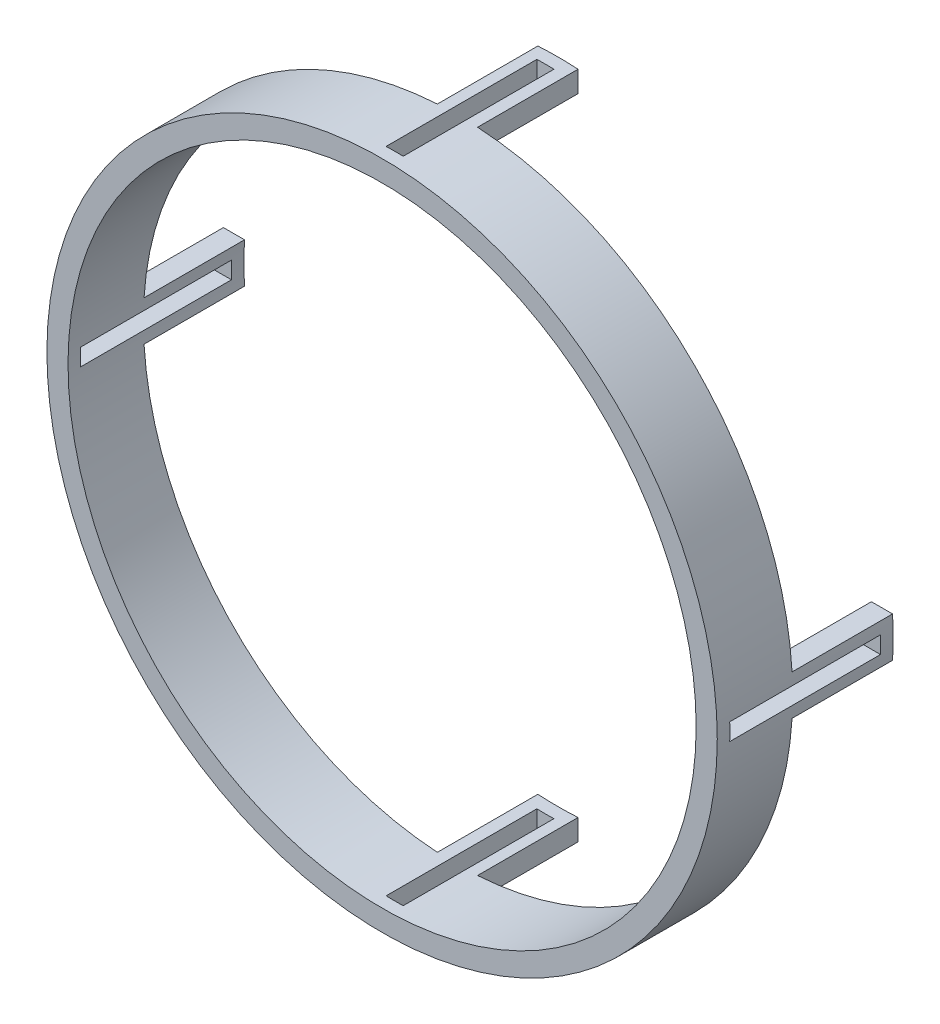
SolidWorks part; units mm, degrees
ref_plane "Front Plane" through (0, 0, 0) normal (0, 0, 1) x (1, 0, 0)
ref_plane "Top Plane" through (0, 0, 0) normal (0, 1, 0) x (1, 0, 0)
ref_plane "Right Plane" through (0, 0, 0) normal (1, 0, 0) x (0, 0, -1)
sketch "Sketch1" plane through (0, 0, 0) normal (0, 0, 1) x (1, 0, 0)
  circle A0 centre (0, 0) radius 79.375
  circle A1 centre (0, 0) radius 84.709
  dimension "D1" = 158.75
  dimension "D2" = 169.418
extrude "Boss-Extrude1" add sketch "Sketch1" along normal blind 19.05
sketch "Sketch3" plane through (0, 0, 0) normal (0, 0, -1) x (-1, 0, 0)
  line L0 (30.8173, 0) -> (-22.3005, 0) construction
  line L1 (0, -12.9993) -> (0, 95.4691) construction
  line L2 (-5.08, 79.2123) -> (-5.08, 84.5565)
  line L3 (5.08, 79.2123) -> (5.08, 84.5565)
  line L4 (-5.08, -79.2123) -> (-5.08, -84.5565)
  line L5 (5.08, -79.2123) -> (5.08, -84.5565)
  line L6 (0, 0) -> (44.2484, -44.2484) construction
  line L7 (79.2123, -5.08) -> (84.5565, -5.08)
  line L8 (79.2123, 5.08) -> (84.5565, 5.08)
  line L9 (-79.2123, 5.08) -> (-84.5565, 5.08)
  line L10 (-79.2123, -5.08) -> (-84.5565, -5.08)
  arc A0 (5.08, 79.2123) -> (-5.08, 79.2123) centre (0, 0) ccw
  circle A2 centre (0, 0) radius 79.375 construction
  arc A3 (5.08, 84.5565) -> (-5.08, 84.5565) centre (0, 0) ccw
  circle A4 centre (0, 0) radius 84.709 construction
  arc A5 (5.08, -79.2123) -> (-5.08, -79.2123) centre (0, 0) cw
  arc A6 (5.08, -84.5565) -> (-5.08, -84.5565) centre (0, 0) cw
  arc A7 (84.5565, -5.08) -> (84.5565, 5.08) centre (0, 0) ccw
  arc A8 (79.2123, -5.08) -> (79.2123, 5.08) centre (0, 0) ccw
  arc A9 (-79.2123, -5.08) -> (-79.2123, 5.08) centre (0, 0) cw
  arc A10 (-84.5565, -5.08) -> (-84.5565, 5.08) centre (0, 0) cw
  dimension "D1" = 5.08
  dimension "D2" = 5.08
  dimension "D3" = 5.08
  dimension "D4" = 5.08
  dimension "D5" = 45
extrude "Boss-Extrude2" add sketch "Sketch3" along normal blind 25.4
sketch "Sketch2" plane through (0, 0, 0) normal (0, 1, 0) x (1, 0, 0)
  line L0 (5.08, 25.4) -> (-5.08, 25.4) construction
  line L1 (0, -2.0807) -> (0, -15.8358) construction
  line L3 (-2.159, -15.875) -> (2.159, -15.875)
  line L4 (-2.159, -15.875) -> (-2.159, 22.225)
  line L5 (-2.159, 22.225) -> (2.159, 22.225)
  line L6 (2.159, -15.875) -> (2.159, 22.225)
  line L7 (-2.159, -15.875) -> (2.159, 22.225) construction
  line L8 (-2.159, 22.225) -> (2.159, -15.875) construction
  point P0 (0, 3.175)
  point P10 (0, 25.4)
  dimension "D1" = 4.318
  dimension "D2" = 38.1
  dimension "D3" = 3.175
ref_axis "Axis1" through (0, 0, 2.0807) along (0, 0, 1)
extrude "Cut-Extrude1" cut sketch "Sketch2" against normal through all
pattern_circular "CirPattern1" count 4 over 360 about axis through (0, 0, 2.0807) along (0, 0, 1) of "Cut-Extrude1"
